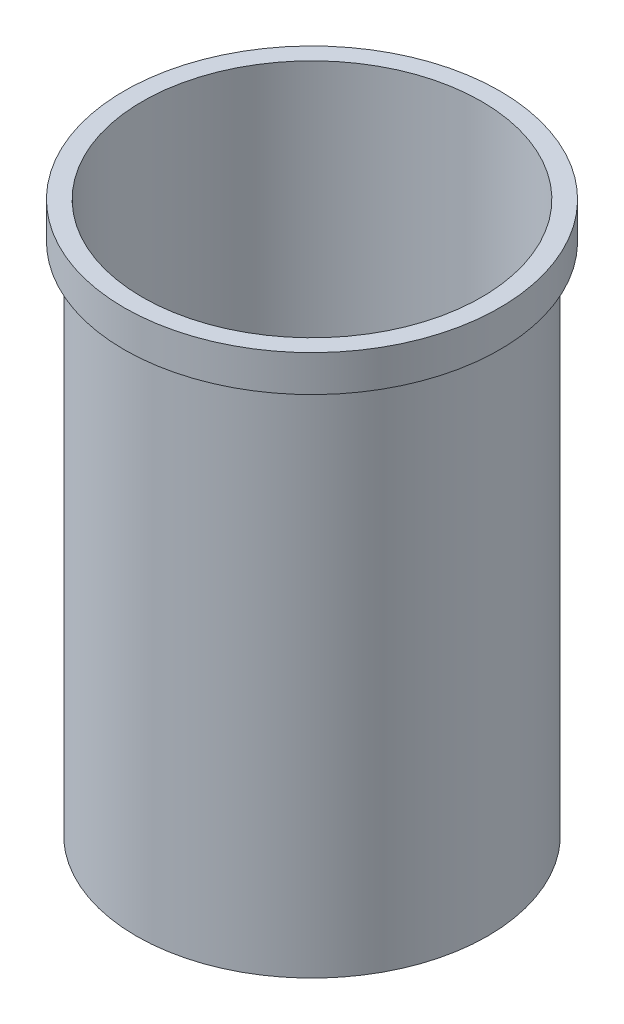
SolidWorks part; units mm, degrees
material "AISI 4340 Steel, normalized"
ref_plane "Front Plane" through (0, 0, 0) normal (0, 0, 1) x (1, 0, 0)
ref_plane "Top Plane" through (0, 0, 0) normal (0, 1, 0) x (1, 0, 0)
ref_plane "Right Plane" through (0, 0, 0) normal (1, 0, 0) x (0, 0, -1)
sketch "Sketch1" plane through (0, 0, 0) normal (0, 1, 0) x (1, 0, 0)
  circle A0 centre (0, 0) radius 58
  circle A1 centre (0, 0) radius 56
  dimension "D1" = 56
  dimension "D2" = 2
extrude "Boss-Extrude1" add sketch "Sketch1" along normal blind 181.66
sketch "Sketch3" plane through (0, 181.66, 0) normal (0, 1, 0) x (1, 0, 0)
  circle A0 centre (0, 0) radius 58 construction
  circle A1 centre (0, 0) radius 58
  circle A2 centre (0, 0) radius 62
  dimension "D1" = 4
extrude "Boss-Extrude2" add sketch "Sketch3" against normal blind 12
equation "\"PS_Radius\"= 108 / 2"
equation "\"PS_Clearance\" = 2"
equation "\"Liner_Radius\"= \"PS_Clearance\" + \"PS_Radius\""
equation "\"D1@Sketch1\"=\"Liner_Radius\""
equation "\"Liner_Thickness\"= 2"
equation "\"D2@Sketch1\"=\"Liner_Thickness\""
equation "\"Cylinder_Length\"= 181.66"
equation "\"D1@Boss-Extrude1\"=\"Cylinder_Length\""
equation "\"Lip_Height\"= 12"
equation "\"D1@Boss-Extrude2\"=\"Lip_Height\""
